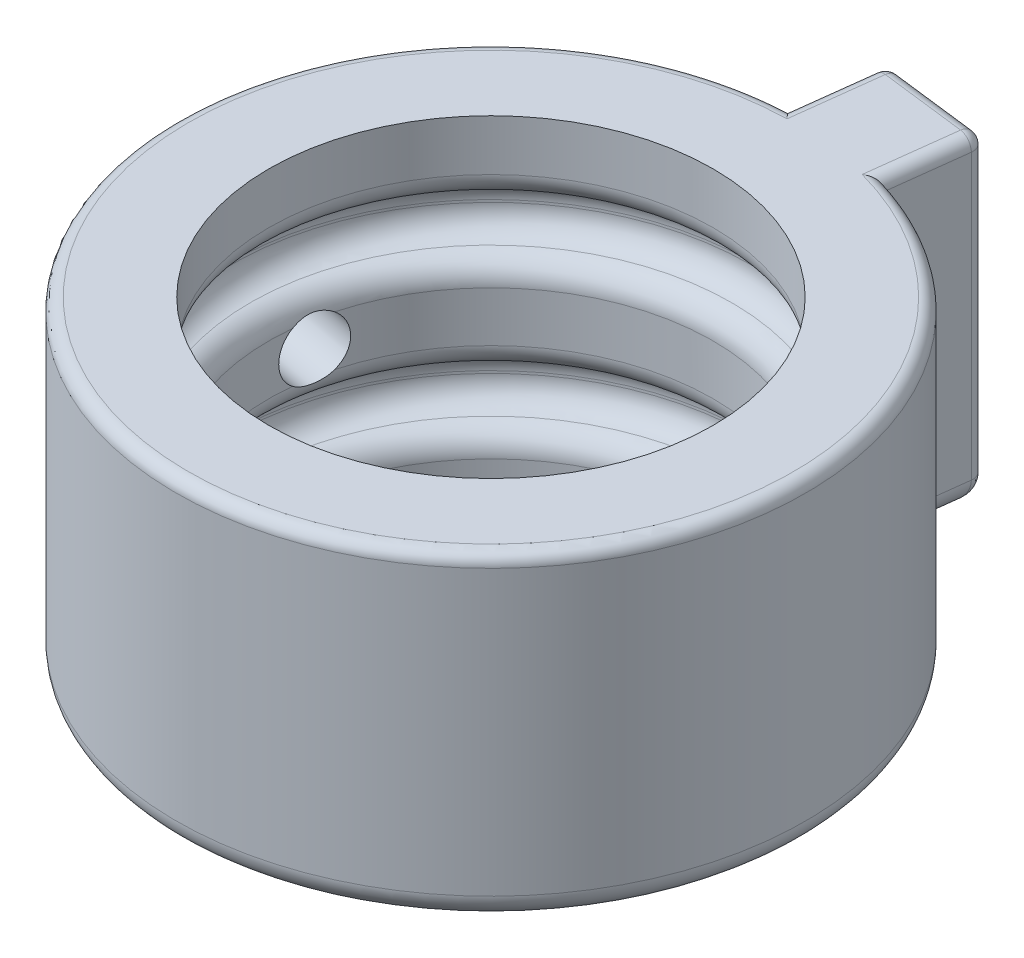
SolidWorks part; units mm, degrees
ref_plane "Спереди" through (0, 0, 0) normal (0, 0, 1) x (1, 0, 0)
ref_plane "Сверху" through (0, 0, 0) normal (0, 1, 0) x (1, 0, 0)
ref_plane "Справа" through (0, 0, 0) normal (1, 0, 0) x (0, 0, -1)
sketch "Эскиз1" plane through (0, 0, 0) normal (0, 1, 0) x (1, 0, 0)
  circle A0 centre (0, 0) radius 9
  circle A1 centre (0, 0) radius 12.75
  dimension "D1" = 18
  dimension "D2" = 25.5
extrude "Бобышка-Вытянуть1" add sketch "Эскиз1" along normal blind 13
sketch "Эскиз2" plane through (0, 13, 0) normal (0, 1, 0) x (1, 0, 0)
  circle A0 centre (0, 0) radius 10.5
  dimension "D1" = 21
extrude "Вырез-Вытянуть1" cut sketch "Эскиз2" against normal blind 2.1 from offset 3 offset against normal yes
extrude "Вырез-Вытянуть2" cut sketch "Эскиз2<2>" against normal blind 2.1 from offset 9 offset against normal yes
sketch "Эскиз2<2>" plane through (0, 13, 0) normal (0, 1, 0) x (1, 0, 0) same geometry as "Эскиз2"
fillet "Скругление1" radius 1 4 edges at (0, 4, 10.5) (0, 10, 10.5) (0, 7.9, 10.5) (0, 1.9, 10.5)
fillet "Скругление2" radius 1 4 edges at (0, 4, 9) (0, 1.9, 9) (0, 7.9, 9) (0, 10, 9)
sketch "Эскиз7" plane through (0, 0, 0) normal (1, 0, 0) x (0, 0, -1)
  line L0 (0, 0) -> (0, 17.7293) construction
ref_plane "Плоскость1" through (0, 0, 0) normal (-0.9833, 0, -0.1822) x (0, 1, 0)
sketch "Эскиз4" plane through (0, 0, 0) normal (-0.9833, 0, -0.1822) x (-0.1822, 0, 0.9833)
  line L0 (0, 6.9635) -> (0, 4.9365) construction
  line L2 (9, 6.9635) -> (-9, 6.9635) construction
  line L3 (9, 4.9365) -> (-9, 4.9365) construction
  circle A0 centre (0, 5.95) radius 1.25
  point P10 (0, 5.95)
  dimension "D1" = 2.5
extrude "Вырез-Вытянуть3" cut sketch "Эскиз4" along normal through all
sketch "Эскиз6" plane through (0, 13, 0) normal (0, 1, 0) x (1, 0, 0)
  line L0 (0, 0) -> (1.9743, 16.0792) construction
  line L2 (0, 0) -> (22.3464, 0) construction
  line L3 (4.2075, 15.805) -> (-0.2589, 16.3535)
  line L4 (4.2075, 15.805) -> (3.7317, 11.93)
  line L6 (-0.2589, 16.3535) -> (-0.7347, 12.4784)
  line L7 (4.2075, 15.805) -> (0.9924, 12.4605) construction
  line L8 (2.0515, 12.3305) -> (-0.2589, 16.3535) construction
  arc A0 (3.7317, 11.93) -> (-0.7347, 12.4784) centre (0, 0) ccw
  point P3 (1.6087, 13.1016)
  point P4 (0, 0)
  point P6 (1.9743, 16.0792)
  dimension "D5" = 12.5
  dimension "D1" = 83
  dimension "D2" = 16.2
  dimension "D3" = 4.5
  dimension "D4" = 3
extrude "Бобышка-Вытянуть2" add sketch "Эскиз6" against normal up to surface (13 mm away) up to face at (0, 0, 12.75)
fillet "Скругление3" radius 0.5 6 edges at (-1.5538, 13, 12.655) (-0.2589, 6.5, -16.3535) (4.2075, 6.5, -15.805) (-0.4814, 13, -14.542) (1.9743, 13, -16.0792) (3.9851, 13, -13.9936)
fillet "Скругление4" radius 1 6 edges at (-1.5538, 0, 12.655) (3.9546, 0, -13.7455) (4.0443, 0, -15.6775) (1.9743, 0, -16.0792) (-0.1314, 0, -16.1903) (-0.5118, 0, -14.2939)
